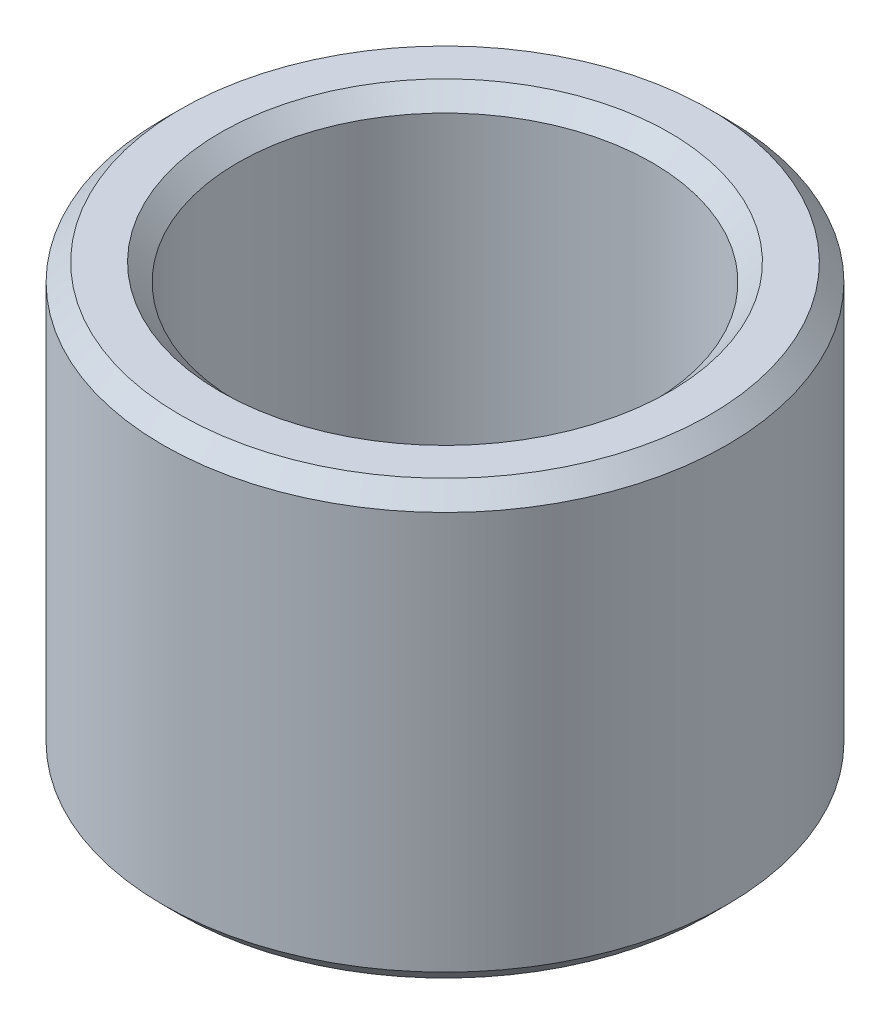
SolidWorks part; units mm, degrees
ref_plane "Front Plane" through (0, 0, 0) normal (0, 0, 1) x (1, 0, 0)
ref_plane "Top Plane" through (0, 0, 0) normal (0, 1, 0) x (1, 0, 0)
ref_plane "Right Plane" through (0, 0, 0) normal (1, 0, 0) x (0, 0, -1)
sketch "Sketch1" plane through (0, 0, 0) normal (0, 1, 0) x (1, 0, 0)
  circle A0 centre (0, 0) radius 10
  dimension "SLEEVE_OD" = 20
extrude "Boss-Extrude1" add sketch "Sketch1" along normal blind 15.3442
sketch "Sketch2" plane through (0, 0, 0) normal (0, 1, 0) x (1, 0, 0)
  circle A0 centre (0, 0) radius 7.3429
  dimension "BORE_D" = 14.6857
extrude "Cut-Extrude1" cut sketch "Sketch2" along normal through all
chamfer "Chamfer1" distance 0.6155 angle 45 4 edges at (0, 15.3442, 7.3429) (0, 0, 7.3429) (0, 0, 10) (0, 15.3442, 10)
